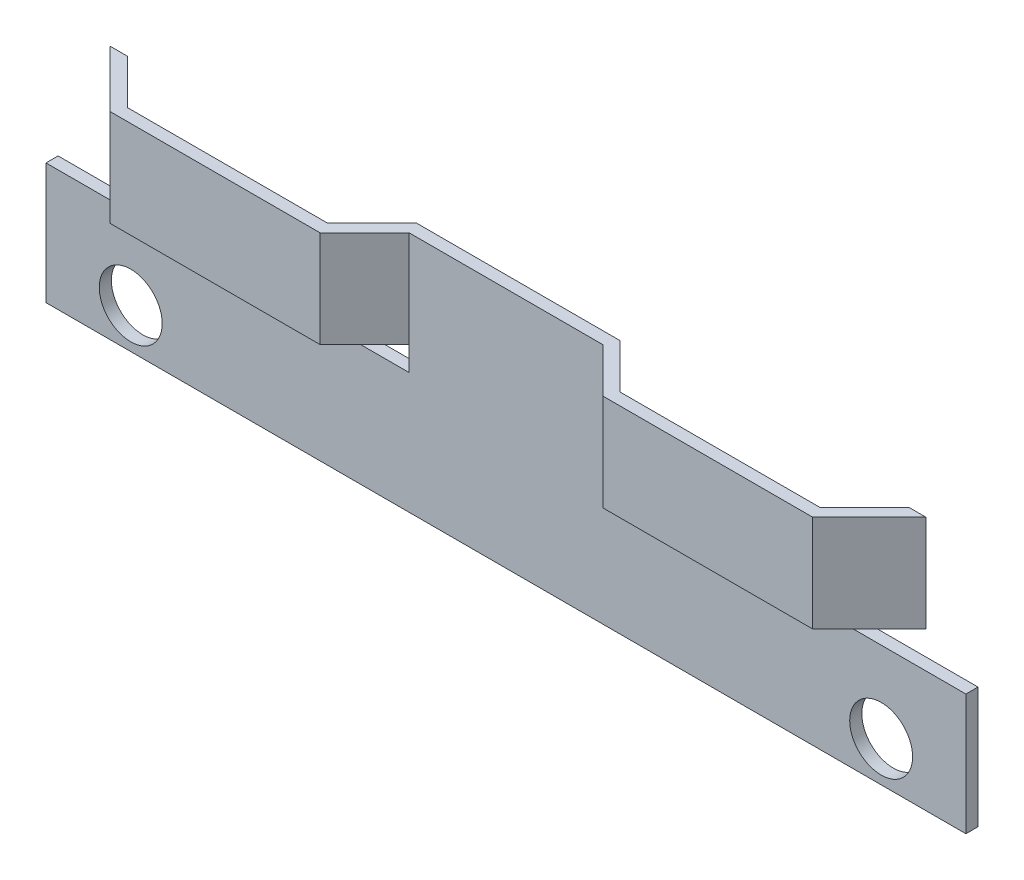
SolidWorks part; units mm, degrees
ref_plane "Front Plane" through (0, 0, 0) normal (0, 0, 1) x (1, 0, 0)
ref_plane "Top Plane" through (0, 0, 0) normal (0, 1, 0) x (1, 0, 0)
ref_plane "Right Plane" through (0, 0, 0) normal (1, 0, 0) x (0, 0, -1)
sketch "Sketch1" plane through (0, 0, 0) normal (0, 0, 1) x (1, 0, 0)
  line L1 (-38, -10) -> (38, -10)
  line L2 (-38, -10) -> (-38, 10)
  line L3 (-38, 10) -> (38, 10)
  line L4 (38, -10) -> (38, 10)
  line L5 (-38, -10) -> (38, 10) construction
  line L6 (-38, 10) -> (38, -10) construction
  point P0 (0, 0)
  dimension "D1" = 76
  dimension "D2" = 20
base flange "Base-Flange1" sketch "Sketch1" thickness 1 reverse thickness direction no parameters "D1"=0.7366
sketch "Sketch6" plane through (0, 0, 0) normal (0, 0, 1) x (1, 0, 0)
  line L0 (0, 0) -> (0, -19.2632) construction
  line L1 (-38, -10) -> (38, -10) construction
  circle A0 centre (-31, -6.7) radius 2.6
  circle A1 centre (31, -6.7) radius 2.6
  dimension "D1" = 5.2
  dimension "D2" = 3.3
  dimension "D3" = 31
extrude "Cut-Extrude1" cut sketch "Sketch6" against normal blind 10 normal cut yes
sketch "Sketch7" plane through (0, 0, 0) normal (0, 0, 1) x (1, 0, 0)
  line L0 (0, 0) -> (0, 22.8908) construction
  line L1 (-38, 10) -> (-8, 10)
  line L2 (-38, 10) -> (-38, 0)
  line L3 (-38, 0) -> (-8, 0)
  line L4 (-8, 10) -> (-8, 0)
  line L5 (8, 10) -> (8, 0)
  line L6 (38, 0) -> (8, 0)
  line L7 (38, 10) -> (38, 0)
  line L8 (38, 10) -> (8, 10)
  dimension "D1" = 10
  dimension "D2" = 30
extrude "Cut-Extrude2" cut sketch "Sketch7" against normal blind 10 normal cut yes
sketch "Sketch8" plane through (0, 10, 0) normal (0, 1, 0) x (1, 0, 0)
  line L0 (8, 0) -> (11.6771, -3.6771)
  line L1 (11.6771, -3.6771) -> (29.0206, -3.6771)
  line L2 (29.0206, -3.6771) -> (33.6977, 1)
  line L3 (38, 1) -> (8, 1) construction
  line L4 (8.4142, 1) -> (12.0913, -2.6771)
  line L5 (12.0913, -2.6771) -> (28.6064, -2.6771)
  line L6 (28.6064, -2.6771) -> (32.2835, 1)
  line L7 (8, 0) -> (8, 1)
  line L8 (8, 1) -> (8.4142, 1)
  line L9 (8.7071, 0.7071) -> (12.0913, -2.6771) construction
  line L10 (32.2835, 1) -> (33.6977, 1)
  line L11 (28.6064, -2.6771) -> (32.9906, 1.7071) construction
  line L12 (0, 1) -> (0, -10.4489) construction
  line L13 (8, 1) -> (-8, 1) construction
  line L14 (-32.2835, 1) -> (-33.6977, 1)
  line L15 (-8, 1) -> (-8.4142, 1)
  line L16 (-8, 0) -> (-8, 1)
  line L17 (-28.6064, -2.6771) -> (-32.2835, 1)
  line L18 (-12.0913, -2.6771) -> (-28.6064, -2.6771)
  line L19 (-8.4142, 1) -> (-12.0913, -2.6771)
  line L20 (-29.0206, -3.6771) -> (-33.6977, 1)
  line L21 (-11.6771, -3.6771) -> (-29.0206, -3.6771)
  line L22 (-8, 0) -> (-11.6771, -3.6771)
  dimension "D1" = 1
extrude "Boss-Extrude1" add sketch "Sketch8" against normal blind 8
sketch "Bend-Lines1" [suppressed] plane through (0, 0, 0) normal (0, 1, 0) x (1, 0, 0)
sketch "Bounding-Box1" [suppressed] plane through (0, 0, 0) normal (0, 1, 0) x (1, 0, 0)
sheet metal parameters "Sheet-Metal1" thickness 1 parameters "D1"=0.7366
flat pattern "Flat-Pattern1" [suppressed]
sketch "Bend-Lines2" plane through (0, 0, 0) normal (0, 1, 0) x (1, 0, 0)
sketch3d "Bounding-Box2" [suppressed]
  line L0 (-38, -12.5, 0) -> (38, -12.5, 0) construction
  line L1 (-38, 12.5, 0) -> (38, 12.5, 0) construction
  line L2 (-38, -12.5, 0) -> (-38, 12.5, 0) construction
  line L3 (38, -12.5, 0) -> (38, 12.5, 0) construction
sheet metal parameters "Sheet-Metal2" thickness 1 parameters "D1"=0.7366
flat pattern "Flat-Pattern1"
sketch "Bend-Lines2" plane through (0, 0, 0) normal (0, 1, 0) x (1, 0, 0)
sketch3d "Bounding-Box2" [suppressed]
  line L0 (-38, -20, 0) -> (38, -20, 0) construction
  line L1 (-38, 20, 0) -> (38, 20, 0) construction
  line L2 (-38, -20, 0) -> (-38, 20, 0) construction
  line L3 (38, -20, 0) -> (38, 20, 0) construction
sheet metal parameters "Sheet-Metal3" thickness 1 parameters "D1"=0.7366
flat pattern "Flat-Pattern1"
sketch "Bend-Lines2" plane through (0, 0, 0) normal (0, 1, 0) x (1, 0, 0)
sketch3d "Bounding-Box2" [suppressed]
  line L0 (-38, -10, 0) -> (38, -10, 0) construction
  line L1 (-38, 10, 0) -> (38, 10, 0) construction
  line L2 (-38, -10, 0) -> (-38, 10, 0) construction
  line L3 (38, -10, 0) -> (38, 10, 0) construction
sheet metal parameters "Sheet-Metal4" thickness 1 parameters "D1"=0.7366
flat pattern "Flat-Pattern1"
sketch "Bend-Lines2" plane through (0, 0, 0) normal (0, 1, 0) x (1, 0, 0)
sketch3d "Bounding-Box2" [suppressed]
  line L0 (-38, -10, 0) -> (38, -10, 0) construction
  line L1 (-38, 10, 0) -> (38, 10, 0) construction
  line L2 (-38, -10, 0) -> (-38, 10, 0) construction
  line L3 (38, -10, 0) -> (38, 10, 0) construction
